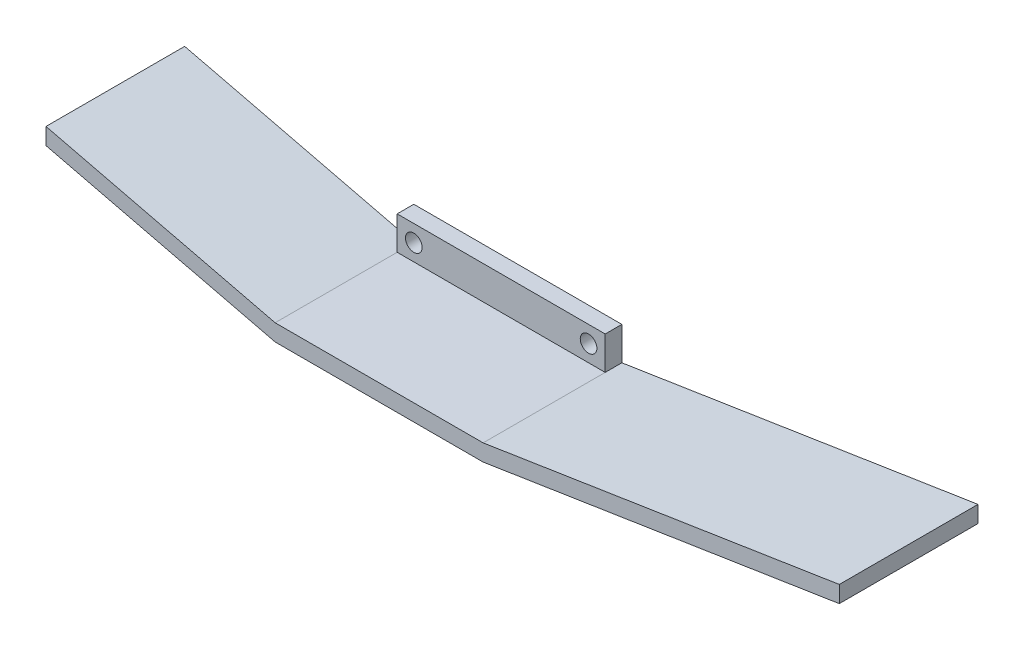
SolidWorks part; units mm, degrees
ref_plane "前视基准面" through (0, 0, 0) normal (0, 0, 1) x (1, 0, 0)
ref_plane "上视基准面" through (0, 0, 0) normal (0, 1, 0) x (1, 0, 0)
ref_plane "右视基准面" through (0, 0, 0) normal (1, 0, 0) x (0, 0, -1)
sketch "草图3" plane through (0, 0, 0) normal (0, 0, 1) x (1, 0, 0)
  line L0 (0, 0) -> (37.5, 0)
  line L1 (37.5, 0) -> (101.7, 10)
  line L2 (0, 0) -> (-41.3, 10)
  line L3 (0, 3) -> (-41.3, 13)
  line L4 (37.5, 3) -> (101.7, 13)
  line L5 (0, 3) -> (0, 9)
  line L6 (0, 9) -> (37.5, 9)
  line L7 (37.5, 9) -> (37.5, 3)
  line L8 (0, 3) -> (37.5, 3)
  line L9 (-41.3, 13) -> (-41.3, 10)
  line L10 (101.7, 13) -> (101.7, 10)
  point P11 (0, 0)
  point P12 (0, 0)
  point P13 (0, 0)
  point P14 (0, 0)
  point P15 (0, 0)
  point P16 (0, 0)
  point P17 (0, 0)
  point P18 (0, 0)
  point P19 (0, 0)
  point P20 (0, 0)
  point P21 (0, 0)
  point P22 (0, 0)
  point P23 (0, 0)
  point P24 (0, 0)
  point P25 (0, 0)
  point P26 (0, 0)
  dimension "D1" = 2
extrude "凸台-拉伸2" add sketch "草图3" along normal blind 25 contours L10 L4 L8 L3 L9 L2 L0 L1 region at (-20.3121, 6.3956, 0)
extrude "凸台-拉伸3" add sketch "草图3<3>" along normal blind 3 contours L5 L8 L7 L6 region at (18.75, 6, 0)
sketch "草图3<3>" plane through (0, 0, 0) normal (0, 0, 1) x (1, 0, 0) same geometry as "草图3"
sketch "草图4" plane through (0, 0, 0) normal (0, 0, -1) x (-1, 0, 0)
  circle A0 centre (-34.5, 6) radius 1.5
  circle A1 centre (-3, 6) radius 1.5
  point P4 (0, 0)
  point P5 (0, 0)
  point P6 (0, 0)
  point P7 (0, 0)
  point P8 (0, 0)
extrude "切除-拉伸2" cut sketch "草图4" against normal blind 4 contours A1 | A0 region at (3, 6, 0)
